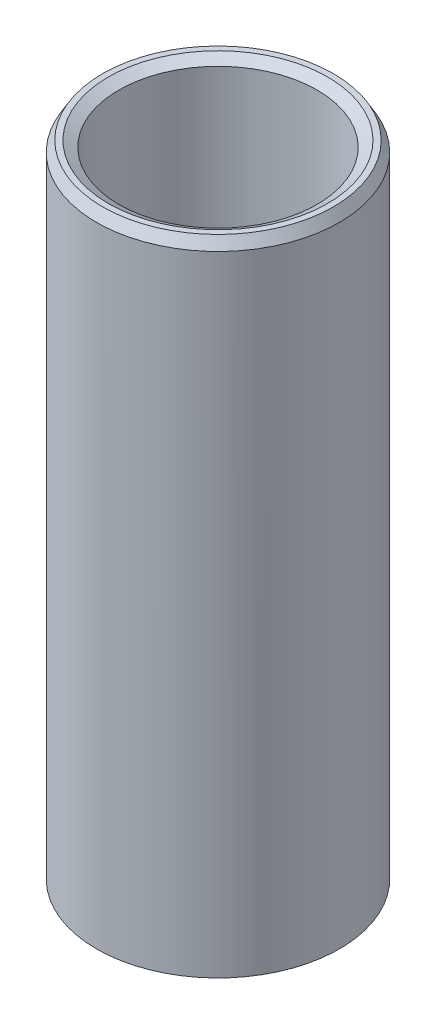
SolidWorks part; units mm, degrees
ref_plane "Front Plane" through (0, 0, 0) normal (0, 0, 1) x (1, 0, 0)
ref_plane "Top Plane" through (0, 0, 0) normal (0, 1, 0) x (1, 0, 0)
ref_plane "Right Plane" through (0, 0, 0) normal (1, 0, 0) x (0, 0, -1)
sketch "Sketch1" plane through (0, 0, 0) normal (0, 1, 0) x (1, 0, 0)
  circle A0 centre (0, 0) radius 45
  dimension "SLEEVE_OD" = 90
extrude "Boss-Extrude1" add sketch "Sketch1" along normal blind 239.2235
sketch "Sketch2" plane through (0, 0, 0) normal (0, 1, 0) x (1, 0, 0)
  circle A0 centre (0, 0) radius 36.7326
  dimension "BORE_D" = 73.4653
extrude "Cut-Extrude1" cut sketch "Sketch2" along normal through all
chamfer "Chamfer1" distance 3.8834 angle 30 4 edges at (0, 239.2235, 36.7326) (0, 0, 36.7326) (0, 0, 45) (0, 239.2235, 45) first distance on face at (0, 239.2235, 36.7326) first distance on face at (0, 0, 36.7326) first distance on face at (0, 239.2235, 45)
